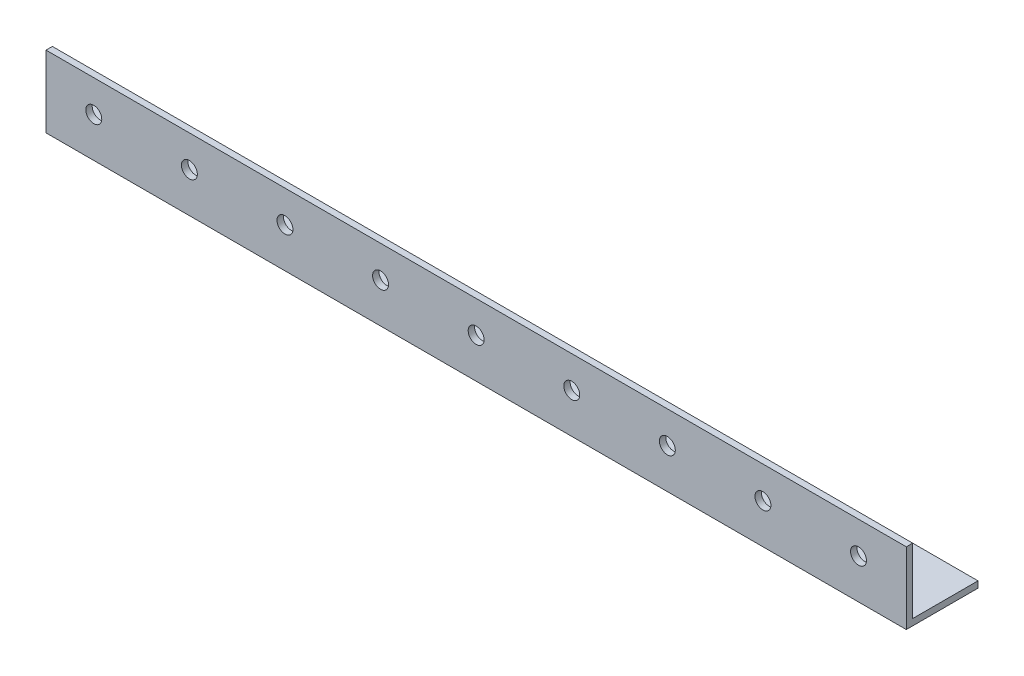
SolidWorks part; units mm, degrees
ref_plane "Спереди" through (0, 0, 0) normal (0, 0, 1) x (1, 0, 0)
ref_plane "Сверху" through (0, 0, 0) normal (0, 1, 0) x (1, 0, 0)
ref_plane "Справа" through (0, 0, 0) normal (1, 0, 0) x (0, 0, -1)
sketch "Эскиз1" plane through (0, 0, 0) normal (1, 0, 0) x (0, 0, -1)
  line L0 (0, 0) -> (0, 45)
  line L1 (0, 0) -> (45, 0)
  dimension "D1" = 45
  dimension "D2" = 45
extrude "Вытянуть-Тонкостенный1" add sketch "Эскиз1" along normal blind 540 thin thin type one direction reverse wall 4
sketch "Эскиз2" plane through (0, 0, 0) normal (0, 0, 1) x (1, 0, 0)
  circle A0 centre (30, 25) radius 5
  circle A1 centre (90, 25) radius 5
  circle A2 centre (150, 25) radius 5
  circle A3 centre (210, 25) radius 5
  circle A8 centre (270, 25) radius 5
  circle A29 centre (330, 25) radius 5
  circle A30 centre (390, 25) radius 5
  circle A31 centre (450, 25) radius 5
  circle A32 centre (510, 25) radius 5
  dimension "D1" = 9
extrude "Вырез-Вытянуть1" cut sketch "Эскиз2" against normal through all
sketch "Эскиз3" plane through (0, 0, 0) normal (0, -1, 0) x (1, 0, 0)
  circle A0 centre (30, -25) radius 5
  circle A1 centre (90, -25) radius 5
  circle A2 centre (150, -25) radius 5
  circle A3 centre (210, -25) radius 5
  circle A4 centre (270, -25) radius 5
  circle A5 centre (330, -25) radius 5
  circle A6 centre (390, -25) radius 5
  circle A7 centre (450, -25) radius 5
  circle A8 centre (510, -25) radius 5
  dimension "D1" = 9
extrude "Вырез-Вытянуть2" cut sketch "Эскиз3" against normal through all
